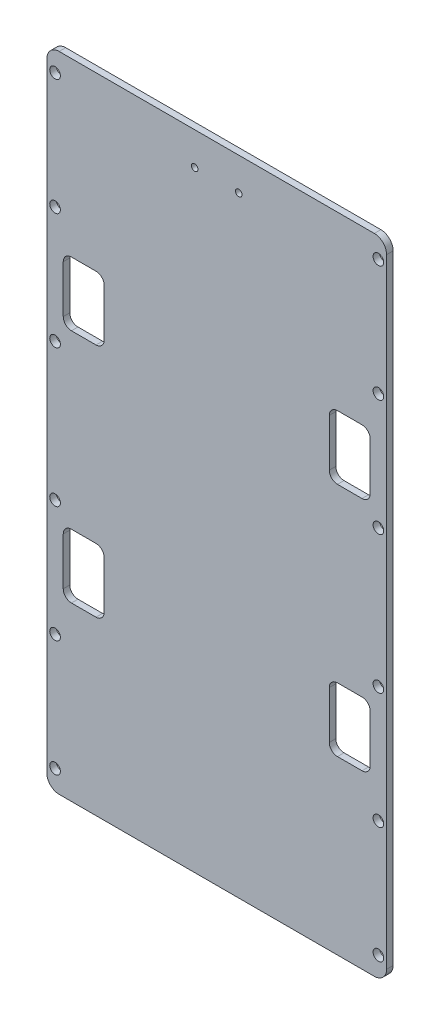
SolidWorks part; units mm, degrees
material "FR4_stuffedProtoboard"
ref_plane "Front Plane" through (0, 0, 0) normal (0, 0, 1) x (1, 0, 0)
ref_plane "Top Plane" through (0, 0, 0) normal (0, 1, 0) x (1, 0, 0)
ref_plane "Right Plane" through (0, 0, 0) normal (1, 0, 0) x (0, 0, -1)
sketch "Sketch1" plane through (0, 0, 0) normal (0, 0, 1) x (1, 0, 0)
  line L0 (-41.5, 0) -> (0, 0) construction
  line L1 (-38.5, 78.6) -> (38.5, 78.6)
  line L2 (-41.5, 75.6) -> (-41.5, -75.6)
  line L3 (-38.5, -78.6) -> (38.5, -78.6)
  line L4 (41.5, 75.6) -> (41.5, -75.6)
  line L5 (0, 0) -> (41.5, 0) construction
  line L7 (-35, 74.6) -> (-20.5, 74.6)
  line L8 (-37.5, 72.1) -> (-37.5, 52.1)
  line L9 (-35, 49.6) -> (-20.5, 49.6)
  line L10 (-18, 72.1) -> (-18, 52.1)
  line L11 (-12.5, 74.6) -> (12.5, 74.6)
  line L12 (-15, 72.1) -> (-15, 52.1)
  line L13 (-12.5, 49.6) -> (12.5, 49.6)
  line L14 (15, 72.1) -> (15, 52.1)
  line L15 (20.5, 74.6) -> (35, 74.6)
  line L16 (18, 72.1) -> (18, 52.1)
  line L17 (20.5, 49.6) -> (35, 49.6)
  line L18 (37.5, 72.1) -> (37.5, 52.1)
  line L19 (-35, 46.6) -> (-20.5, 46.6)
  line L20 (-37.5, 44.1) -> (-37.5, 21.1)
  line L21 (-35, 18.6) -> (-20.5, 18.6)
  line L22 (-18, 44.1) -> (-18, 21.1)
  line L23 (-12.5, 46.6) -> (12.5, 46.6)
  line L24 (-15, 44.1) -> (-15, 21.1)
  line L25 (-12.5, 18.6) -> (12.5, 18.6)
  line L26 (15, 44.1) -> (15, 21.1)
  line L27 (20.5, 46.6) -> (35, 46.6)
  line L28 (18, 44.1) -> (18, 21.1)
  line L29 (20.5, 18.6) -> (35, 18.6)
  line L30 (37.5, 44.1) -> (37.5, 21.1)
  line L31 (-35, 15.6) -> (-20.5, 15.6)
  line L32 (-37.5, 13.1) -> (-37.5, -13.1)
  line L33 (-35, -15.6) -> (-20.5, -15.6)
  line L34 (-18, 13.1) -> (-18, -13.1)
  line L35 (-12.5, 15.6) -> (12.5, 15.6)
  line L36 (-15, 13.1) -> (-15, -13.1)
  line L37 (-12.5, -15.6) -> (12.5, -15.6)
  line L38 (15, 13.1) -> (15, -13.1)
  line L39 (20.5, 15.6) -> (35, 15.6)
  line L40 (18, 13.1) -> (18, -13.1)
  line L41 (20.5, -15.6) -> (35, -15.6)
  line L42 (37.5, 13.1) -> (37.5, -13.1)
  line L43 (-35, -18.6) -> (-20.5, -18.6)
  line L44 (-37.5, -21.1) -> (-37.5, -44.1)
  line L45 (-35, -46.6) -> (-20.5, -46.6)
  line L46 (-18, -21.1) -> (-18, -44.1)
  line L47 (-12.5, -18.6) -> (12.5, -18.6)
  line L48 (-15, -21.1) -> (-15, -44.1)
  line L49 (-12.5, -46.6) -> (12.5, -46.6)
  line L50 (15, -21.1) -> (15, -44.1)
  line L51 (20.5, -18.6) -> (35, -18.6)
  line L52 (18, -21.1) -> (18, -44.1)
  line L53 (20.5, -46.6) -> (35, -46.6)
  line L54 (37.5, -21.1) -> (37.5, -44.1)
  line L55 (-35, -49.6) -> (-20.5, -49.6)
  line L56 (-37.5, -52.1) -> (-37.5, -72.1)
  line L57 (-35, -74.6) -> (-20.5, -74.6)
  line L58 (-18, -52.1) -> (-18, -72.1)
  line L59 (-12.5, -49.6) -> (12.5, -49.6)
  line L60 (-15, -52.1) -> (-15, -72.1)
  line L61 (-12.5, -74.6) -> (12.5, -74.6)
  line L62 (15, -52.1) -> (15, -72.1)
  line L63 (20.5, -49.6) -> (35, -49.6)
  line L64 (18, -52.1) -> (18, -72.1)
  line L65 (20.5, -74.6) -> (35, -74.6)
  line L66 (37.5, -52.1) -> (37.5, -72.1)
  arc A0 (-41.5, -75.6) -> (-38.5, -78.6) centre (-38.5, -75.6) ccw
  arc A1 (38.5, -78.6) -> (41.5, -75.6) centre (38.5, -75.6) ccw
  arc A2 (38.5, 78.6) -> (41.5, 75.6) centre (38.5, 75.6) cw
  arc A3 (-38.5, 78.6) -> (-41.5, 75.6) centre (-38.5, 75.6) ccw
  arc A4 (-20.5, 49.6) -> (-18, 52.1) centre (-20.5, 52.1) ccw
  arc A5 (-20.5, 74.6) -> (-18, 72.1) centre (-20.5, 72.1) cw
  arc A6 (-35, 74.6) -> (-37.5, 72.1) centre (-35, 72.1) ccw
  arc A7 (-20.5, -18.6) -> (-18, -21.1) centre (-20.5, -21.1) cw
  arc A8 (-35, -18.6) -> (-37.5, -21.1) centre (-35, -21.1) ccw
  arc A9 (-37.5, -44.1) -> (-35, -46.6) centre (-35, -44.1) ccw
  arc A10 (-20.5, -46.6) -> (-18, -44.1) centre (-20.5, -44.1) ccw
  arc A11 (-15, -44.1) -> (-12.5, -46.6) centre (-12.5, -44.1) ccw
  arc A12 (-12.5, -18.6) -> (-15, -21.1) centre (-12.5, -21.1) ccw
  arc A13 (12.5, -18.6) -> (15, -21.1) centre (12.5, -21.1) cw
  arc A14 (12.5, -46.6) -> (15, -44.1) centre (12.5, -44.1) ccw
  arc A15 (18, -44.1) -> (20.5, -46.6) centre (20.5, -44.1) ccw
  arc A16 (20.5, -18.6) -> (18, -21.1) centre (20.5, -21.1) ccw
  arc A17 (35, -18.6) -> (37.5, -21.1) centre (35, -21.1) cw
  arc A18 (35, -46.6) -> (37.5, -44.1) centre (35, -44.1) ccw
  arc A19 (35, -49.6) -> (37.5, -52.1) centre (35, -52.1) cw
  arc A20 (35, -74.6) -> (37.5, -72.1) centre (35, -72.1) ccw
  arc A21 (18, -72.1) -> (20.5, -74.6) centre (20.5, -72.1) ccw
  arc A22 (20.5, -49.6) -> (18, -52.1) centre (20.5, -52.1) ccw
  arc A23 (12.5, -49.6) -> (15, -52.1) centre (12.5, -52.1) cw
  arc A24 (12.5, -74.6) -> (15, -72.1) centre (12.5, -72.1) ccw
  arc A25 (-15, -72.1) -> (-12.5, -74.6) centre (-12.5, -72.1) ccw
  arc A26 (-12.5, -49.6) -> (-15, -52.1) centre (-12.5, -52.1) ccw
  arc A27 (-20.5, -49.6) -> (-18, -52.1) centre (-20.5, -52.1) cw
  arc A28 (-35, -49.6) -> (-37.5, -52.1) centre (-35, -52.1) ccw
  arc A29 (-37.5, -72.1) -> (-35, -74.6) centre (-35, -72.1) ccw
  arc A30 (-20.5, -74.6) -> (-18, -72.1) centre (-20.5, -72.1) ccw
  arc A31 (-37.5, -13.1) -> (-35, -15.6) centre (-35, -13.1) ccw
  arc A32 (-35, 15.6) -> (-37.5, 13.1) centre (-35, 13.1) ccw
  arc A33 (-20.5, 15.6) -> (-18, 13.1) centre (-20.5, 13.1) cw
  arc A34 (-20.5, -15.6) -> (-18, -13.1) centre (-20.5, -13.1) ccw
  arc A35 (-15, -13.1) -> (-12.5, -15.6) centre (-12.5, -13.1) ccw
  arc A36 (-12.5, 15.6) -> (-15, 13.1) centre (-12.5, 13.1) ccw
  arc A37 (12.5, 15.6) -> (15, 13.1) centre (12.5, 13.1) cw
  arc A38 (12.5, -15.6) -> (15, -13.1) centre (12.5, -13.1) ccw
  arc A39 (18, -13.1) -> (20.5, -15.6) centre (20.5, -13.1) ccw
  arc A40 (35, -15.6) -> (37.5, -13.1) centre (35, -13.1) ccw
  arc A41 (20.5, 15.6) -> (18, 13.1) centre (20.5, 13.1) ccw
  arc A42 (35, 15.6) -> (37.5, 13.1) centre (35, 13.1) cw
  arc A43 (35, 18.6) -> (37.5, 21.1) centre (35, 21.1) ccw
  arc A44 (18, 21.1) -> (20.5, 18.6) centre (20.5, 21.1) ccw
  arc A45 (20.5, 46.6) -> (18, 44.1) centre (20.5, 44.1) ccw
  arc A46 (35, 46.6) -> (37.5, 44.1) centre (35, 44.1) cw
  arc A47 (35, 49.6) -> (37.5, 52.1) centre (35, 52.1) ccw
  arc A48 (35, 74.6) -> (37.5, 72.1) centre (35, 72.1) cw
  arc A49 (18, 52.1) -> (20.5, 49.6) centre (20.5, 52.1) ccw
  arc A50 (20.5, 74.6) -> (18, 72.1) centre (20.5, 72.1) ccw
  arc A51 (12.5, 49.6) -> (15, 52.1) centre (12.5, 52.1) ccw
  arc A52 (12.5, 74.6) -> (15, 72.1) centre (12.5, 72.1) cw
  arc A53 (-12.5, 74.6) -> (-15, 72.1) centre (-12.5, 72.1) ccw
  arc A54 (-15, 52.1) -> (-12.5, 49.6) centre (-12.5, 52.1) ccw
  arc A55 (12.5, 18.6) -> (15, 21.1) centre (12.5, 21.1) ccw
  arc A56 (12.5, 46.6) -> (15, 44.1) centre (12.5, 44.1) cw
  arc A57 (-12.5, 46.6) -> (-15, 44.1) centre (-12.5, 44.1) ccw
  arc A58 (-15, 21.1) -> (-12.5, 18.6) centre (-12.5, 21.1) ccw
  arc A59 (-37.5, 21.1) -> (-35, 18.6) centre (-35, 21.1) ccw
  arc A60 (-20.5, 18.6) -> (-18, 21.1) centre (-20.5, 21.1) ccw
  arc A61 (-20.5, 46.6) -> (-18, 44.1) centre (-20.5, 44.1) cw
  arc A62 (-35, 46.6) -> (-37.5, 44.1) centre (-35, 44.1) ccw
  arc A63 (-37.5, 52.1) -> (-35, 49.6) centre (-35, 52.1) ccw
  point P72 (41.5, -78.6)
  point P75 (41.5, 78.6)
  point P78 (-41.5, 78.6)
  point P159 (37.5, 18.6)
  point P166 (37.5, 46.6)
  point P169 (37.5, 49.6)
  point P172 (37.5, 74.6)
  point P181 (15, 74.6)
  point P184 (-15, 74.6)
  dimension "D16" = 3
  dimension "D17" = 2.5
  dimension "D18" = 2.5
  dimension "D1" = 3
  dimension "D2" = 3
  dimension "D3" = 3
  dimension "D4" = 3
  dimension "D5" = 3
  dimension "D6" = 3
  dimension "D7" = 4
  dimension "D8" = 4
  dimension "D9" = 4
  dimension "D10" = 4
  dimension "D11" = 157.2
  dimension "D12" = 83
  dimension "D13" = 30
  dimension "D14" = 25
  dimension "D15" = 28
extrude "General Shape" add sketch "Sketch1" along normal blind 1.6 contours L8 A63 L9 A4 L10 A5 L7 A6 | L12 A54 L13 A51 L14 A52 L11 A53 | L15 A50 L16 A49 L17 A47 L18 A48 | L1 A3 L2 A0 L3 A1 L4 A2 A63 L8 A6 L7 A5 L10 A4 L9 A62 L19 A61 L22 A60 L21 A59 L20 A58 L24 A57 L23 A56 L26 A55 L25 A54 L12 A53 L11 A52 L14 A51 L13 A50 L15 A48 L18 A47 L17 | L24 A58 L25 A55 L26 A56 L23 A57 | L19 A62 L20 A59 L21 A60 L22 A61 | A46 L27 A45 L28 A44 L29 A43 L30 | A42 L39 A41 L40 A39 L41 A40 L42 | L37 A38 L38 A37 L35 A36 L36 A35 | L33 A34 L34 A33 L31 A32 L32 A31 | L45 A10 L46 A7 L43 A8 L44 A9 | L49 A14 L50 A13 L47 A12 L48 A11 | L53 A18 L54 A17 L51 A16 L52 A15 | L63 A22 L64 A21 L65 A20 L66 A19 | L59 A26 L60 A25 L61 A24 L62 A23 | L57 A30 L58 A27 L55 A28 L56 A29 region at (0, 76.8223, 0) region at (-27.75, 62.1, 0) region at (0, 62.1, 0) region at (27.75, 62.1, 0) region at (-27.75, 32.6, 0) region at (0, 32.6, 0) region at (27.75, 32.6, 0) region at (-27.75, 0, 0) region at (0, 0, 0) region at (27.75, 0, 0) region at (-27.75, -32.6, 0) region at (0, -32.6, 0) region at (27.75, -32.6, 0) region at (-27.75, -62.1, 0) region at (0, -62.1, 0) region at (27.75, -62.1, 0)
sketch "Sketch2" plane through (0, 0, 0) normal (0, 0, -1) x (-1, 0, 0)
  line L0 (38.5, 78.6) -> (-38.5, 78.6) construction
  line L1 (-22, 64) -> (0, 64) construction
  line L2 (-41.5, 75.6) -> (-41.5, -75.6) construction
  line L3 (-22, 64) -> (-22, 54) construction
  line L4 (-22, -71.6) -> (0, -71.6) construction
  line L5 (-22, -71.6) -> (-22, -61.6) construction
  line L7 (38.5, -78.6) -> (-38.5, -78.6) construction
  line L8 (-41.5, 75.6) -> (-41.5, -75.6) construction
  circle A0 centre (-22, 64) radius 1.2
  circle A1 centre (0, 64) radius 1.2
  circle A2 centre (22, 64) radius 1.2
  circle A3 centre (0, 54) radius 1.2
  circle A4 centre (22, 54) radius 1.2
  circle A5 centre (0, 44) radius 1.2
  circle A6 centre (22, 44) radius 1.2
  circle A7 centre (0, 34) radius 1.2
  circle A8 centre (22, 34) radius 1.2
  circle A9 centre (0, 24) radius 1.2
  circle A10 centre (22, 24) radius 1.2
  circle A11 centre (-22, 54) radius 1.2
  circle A12 centre (-22, 44) radius 1.2
  circle A13 centre (-22, 34) radius 1.2
  circle A14 centre (-22, 24) radius 1.2
  circle A15 centre (-22, -71.6) radius 1.2
  circle A16 centre (0, -71.6) radius 1.2
  circle A17 centre (22, -71.6) radius 1.2
  circle A18 centre (0, -61.6) radius 1.2
  circle A19 centre (22, -61.6) radius 1.2
  circle A20 centre (0, -51.6) radius 1.2
  circle A21 centre (22, -51.6) radius 1.2
  circle A22 centre (0, -41.6) radius 1.2
  circle A23 centre (22, -41.6) radius 1.2
  circle A24 centre (0, -31.6) radius 1.2
  circle A25 centre (22, -31.6) radius 1.2
  circle A26 centre (0, -21.6) radius 1.2
  circle A27 centre (22, -21.6) radius 1.2
  circle A28 centre (-22, -61.6) radius 1.2
  circle A29 centre (-22, -51.6) radius 1.2
  circle A30 centre (-22, -41.6) radius 1.2
  circle A31 centre (-22, -31.6) radius 1.2
  circle A32 centre (-22, -21.6) radius 1.2
  dimension "D3" = 2.4
  dimension "D9" = 2.4
  dimension "D1" = 14.6
  dimension "D2" = 19.5
  dimension "D6" = 90
  dimension "D7" = 22
  dimension "D8" = 10
  dimension "D10" = 7
  dimension "D11" = 19.5
  dimension "D14" = 90
  dimension "D15" = 22
  dimension "D16" = 10
  dimension "D4" = 3
  dimension "D5" = 5
  dimension "D12" = 3
  dimension "D13" = 6
hole_wizard "M2 Clearance Hole1" positions "3DSketch1" profile "Sketch4" hole size "M2" standard "ANSI Metric" end condition up to next
sketch3d "3DSketch1"
  line L0 (-39.5, 73.6, 0) -> (-39.5, 45.2, 0) construction
  line L1 (-39.5, 45.2, 0) -> (-39.5, 16.8, 0) construction
  line L3 (-41.5, 75.6, 0) -> (-41.5, -75.6, 0) construction
  line L4 (-38.5, 78.6, 0) -> (38.5, 78.6, 0) construction
  point P0 (-39.5, 73.6, 0)
  point P2 (-39.5, 45.2, 0)
  point P4 (-39.5, 16.8, 0)
  dimension "D1" = 2
  dimension "D2" = 5
  dimension "D3" = 28.4
sketch "Sketch4" plane through (-39.5, 73.6, 0) normal (1, 0, 0) x (0, 1, 0)
  line L0 (0, 0) -> (0, 1.6)
  line L1 (0, 1.6) -> (1.3, 1.6)
  line L2 (1.3, 1.6) -> (1.3, 0)
  line L5 (1.3, 0) -> (0, 0)
  line L11 (0, -6.35) -> (0, 107.95) construction
  dimension "Thru Hole Dia." = 2.6
  dimension "Thru Hole Depth" = 1.6
mirror "Mirror1" about plane through (0, 0, 0) normal (1, 0, 0) of "M2 Clearance Hole1"
mirror "Mirror2" about plane through (0, 0, 0) normal (0, 1, 0) of "Mirror1"
sketch "Sketch5" plane through (0, 0, 0) normal (0, 0, -1) x (-1, 0, 0)
  line L0 (12.5, 74.6) -> (-12.5, 74.6) construction
  line L1 (-5, 73.6) -> (5, 73.6)
  line L2 (-7.5, 71.1) -> (-7.5, 70.1)
  line L3 (-5, 67.6) -> (5, 67.6)
  line L4 (7.5, 71.1) -> (7.5, 70.1)
  line L5 (15, 72.1) -> (15, 52.1) construction
  line L6 (-7, 68.6) -> (7, 68.6)
  arc A0 (5, 73.6) -> (7.5, 71.1) centre (5, 71.1) cw
  arc A1 (5, 67.6) -> (7.5, 70.1) centre (5, 70.1) ccw
  arc A2 (-7.5, 70.1) -> (-5, 67.6) centre (-5, 70.1) ccw
  arc A3 (-5, 73.6) -> (-7.5, 71.1) centre (-5, 71.1) ccw
  circle A4 centre (-5.38, 70.6) radius 0.8
  circle A5 centre (5.38, 70.6) radius 0.8
  point P6 (7.5, 73.6)
  point P9 (7.5, 67.6)
  point P14 (-7.5, 73.6)
  dimension "D3" = 2.5
  dimension "D5" = 1.6
  dimension "D6" = 2.12
  dimension "D1" = 6
  dimension "D2" = 15
  dimension "D4" = 1
  dimension "D7" = 2.12
  dimension "D8" = 7.5
  dimension "D9" = 3
  dimension "D10" = 3
  dimension "D11" = 14
extrude "Connector holes" cut sketch "Sketch5" against normal through all contours A4 | A5 region at (5.38, 70.6, 0) region at (-5.38, 70.6, 0)
sketch "Sketch6" plane through (0, 0, 0) normal (0, 0, -1) x (-1, 0, 0)
  line L0 (38.5, -78.6) -> (-38.5, -78.6) construction
  line L1 (-35.5, 36.6) -> (-29.5, 36.6)
  line L2 (-37.5, 34.6) -> (-37.5, 23)
  line L3 (-35.5, 21) -> (-29.5, 21)
  line L4 (-27.5, 34.6) -> (-27.5, 23)
  line L5 (29.5, 36.6) -> (35.5, 36.6)
  line L6 (27.5, 34.6) -> (27.5, 23)
  line L7 (29.5, 21) -> (35.5, 21)
  line L8 (37.5, 34.6) -> (37.5, 23)
  line L9 (-35.5, -21) -> (-29.5, -21)
  line L10 (-37.5, -23) -> (-37.5, -34.6)
  line L11 (-35.5, -36.6) -> (-29.5, -36.6)
  line L12 (-27.5, -23) -> (-27.5, -34.6)
  line L13 (29.5, -21) -> (35.5, -21)
  line L14 (27.5, -23) -> (27.5, -34.6)
  line L15 (29.5, -36.6) -> (35.5, -36.6)
  line L16 (37.5, -23) -> (37.5, -34.6)
  line L17 (38.5, 78.6) -> (-38.5, 78.6) construction
  line L18 (-41.5, 75.6) -> (-41.5, -75.6) construction
  line L19 (41.5, 75.6) -> (41.5, -75.6) construction
  arc A0 (-37.5, 23) -> (-35.5, 21) centre (-35.5, 23) ccw
  arc A1 (-29.5, 21) -> (-27.5, 23) centre (-29.5, 23) ccw
  arc A2 (-29.5, 36.6) -> (-27.5, 34.6) centre (-29.5, 34.6) cw
  arc A3 (-35.5, 36.6) -> (-37.5, 34.6) centre (-35.5, 34.6) ccw
  arc A4 (-37.5, -34.6) -> (-35.5, -36.6) centre (-35.5, -34.6) ccw
  arc A5 (-29.5, -36.6) -> (-27.5, -34.6) centre (-29.5, -34.6) ccw
  arc A6 (-29.5, -21) -> (-27.5, -23) centre (-29.5, -23) cw
  arc A7 (-35.5, -21) -> (-37.5, -23) centre (-35.5, -23) ccw
  arc A8 (27.5, -34.6) -> (29.5, -36.6) centre (29.5, -34.6) ccw
  arc A9 (35.5, -21) -> (37.5, -23) centre (35.5, -23) cw
  arc A10 (29.5, -21) -> (27.5, -23) centre (29.5, -23) ccw
  arc A11 (35.5, -36.6) -> (37.5, -34.6) centre (35.5, -34.6) ccw
  arc A12 (35.5, 21) -> (37.5, 23) centre (35.5, 23) ccw
  arc A13 (35.5, 36.6) -> (37.5, 34.6) centre (35.5, 34.6) cw
  arc A14 (29.5, 36.6) -> (27.5, 34.6) centre (29.5, 34.6) ccw
  arc A15 (27.5, 23) -> (29.5, 21) centre (29.5, 23) ccw
  dimension "D7" = 2
  dimension "D8" = 2
  dimension "D9" = 2
  dimension "D10" = 2
  dimension "D11" = 2
  dimension "D1" = 42
  dimension "D2" = 42
  dimension "D3" = 4
  dimension "D4" = 10
  dimension "D5" = 4
  dimension "D6" = 42
extrude "Star Tracker Cutouts" cut sketch "Sketch6" against normal through all
